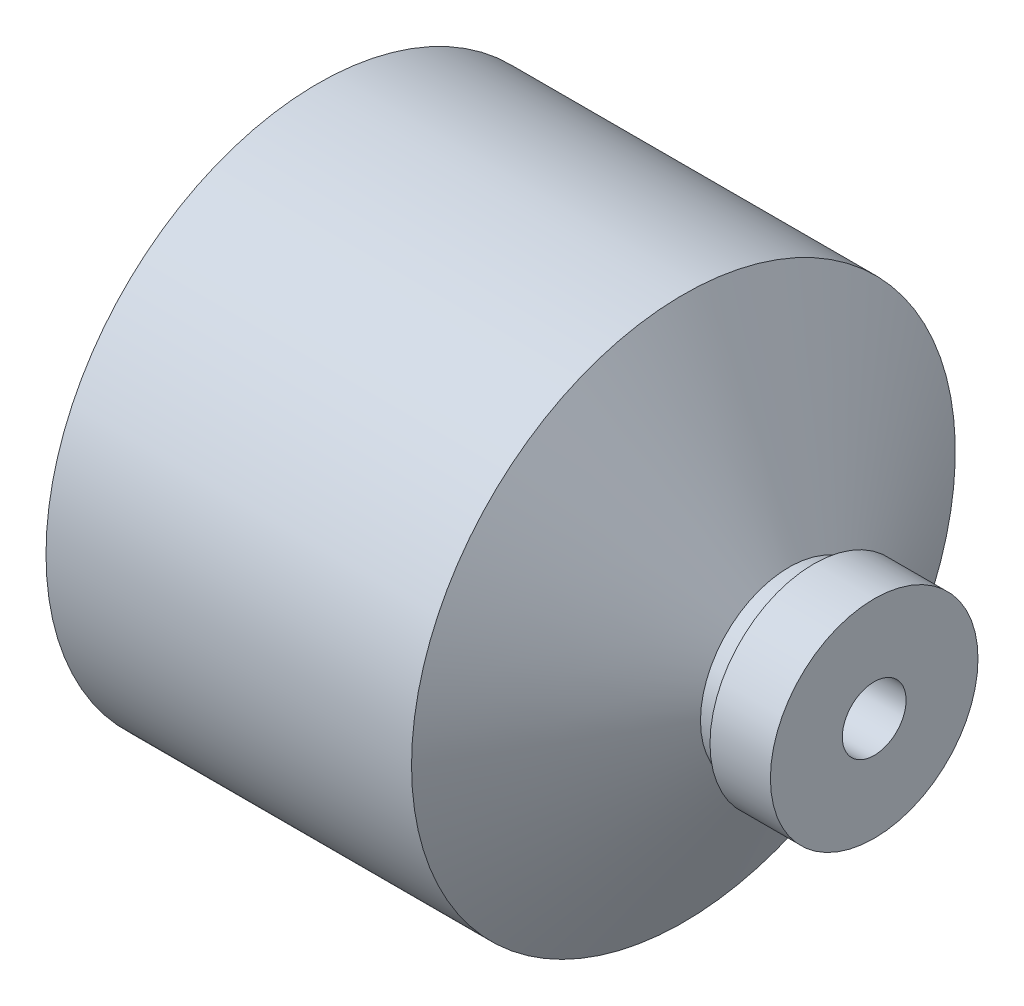
SolidWorks part; units mm, degrees
ref_plane "Front Plane" through (0, 0, 0) normal (0, 0, 1) x (1, 0, 0)
ref_plane "Top Plane" through (0, 0, 0) normal (0, 1, 0) x (1, 0, 0)
ref_plane "Right Plane" through (0, 0, 0) normal (1, 0, 0) x (0, 0, -1)
sketch "Sketch1" plane through (0, 0, 0) normal (0, 1, 0) x (1, 0, 0)
  line L0 (-73.662, 36) -> (-25.2624, 36)
  line L1 (-73.662, 36) -> (-73.662, 0) construction
  line L2 (0, 13.7437) -> (0, 0) construction
  line L3 (-73.662, 33.75) -> (-32.662, 33.75)
  line L4 (-73.662, 36) -> (-73.662, 33.75)
  line L6 (-73.662, 0) -> (0, 0) construction
  line L8 (-23.662, 24.75) -> (-23.662, 1.6)
  line L15 (0, 13.7437) -> (0, 4.225)
  line L16 (0, 4.225) -> (-9.8, 4.225)
  line L18 (-32.662, 33.75) -> (-23.662, 24.75)
  line L20 (-23.662, 1.6) -> (-13.662, 1.6)
  line L21 (-13.662, 1.6) -> (-13.662, 1)
  line L22 (-13.662, 1) -> (-11.662, 1)
  line L23 (-11.662, 1) -> (-9.8, 4.225)
  line L25 (0, 13.7437) -> (-8, 13.7437)
  line L26 (-8, 13.7437) -> (-9.1547, 11.7437)
  line L27 (-9.1547, 11.7437) -> (-11.258, 11.7437)
  line L28 (-11.258, 11.7437) -> (-25.2624, 36)
  line L29 (-23.662, 1.6) -> (-30.662, 1.6) construction
  line L30 (-30.662, 1.6) -> (-30.662, 0) construction
  dimension "D2" = 36
  dimension "D3" = 33.75
  dimension "D4" = 9
  dimension "D5" = 45
  dimension "D6" = 50
  dimension "D7" = 4.225
  dimension "D8" = 9.8
  dimension "D9" = 30
  dimension "D10" = 30
  dimension "D11" = 30
  dimension "D12" = 2
  dimension "D14" = 8
  dimension "D15" = 1
  dimension "D16" = 2
  dimension "D17" = 1.6
  dimension "D18" = 7
  dimension "D19" = 10
revolve "Revolve1" add sketch "Sketch1" angle 360 about L6
equation "\"D3@Sketch1\"=67.5/2"
